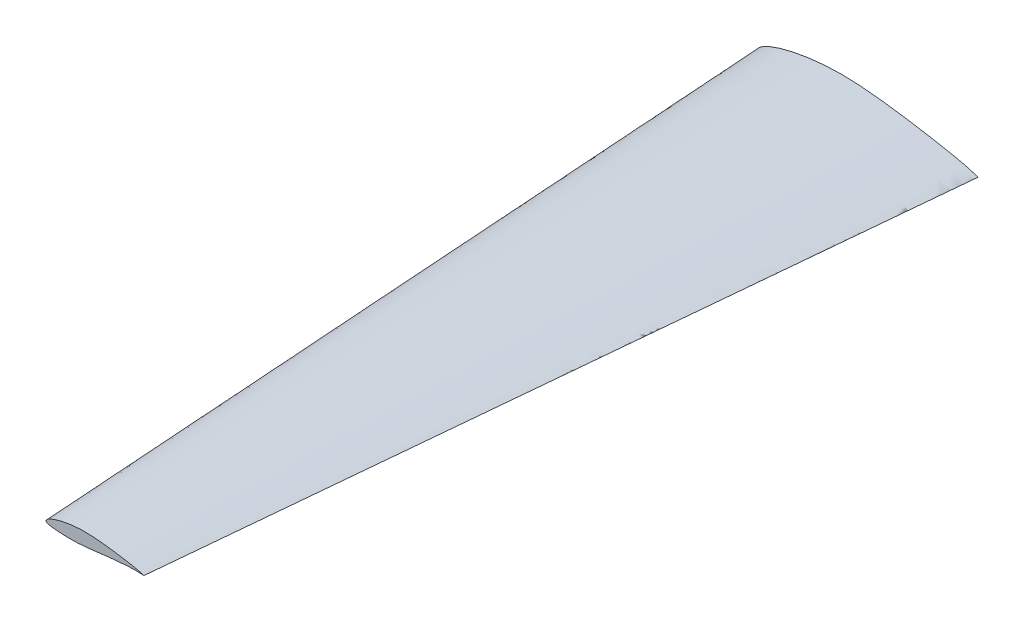
SolidWorks part; units mm, degrees
ref_plane "Front Plane" through (0, 0, 0) normal (0, 0, 1) x (1, 0, 0)
ref_plane "Top Plane" through (0, 0, 0) normal (0, 1, 0) x (1, 0, 0)
ref_plane "Right Plane" through (0, 0, 0) normal (1, 0, 0) x (0, 0, -1)
curve "Curve1"
  spline degree 3 poles (0.9921, 0.0008, 0) (1.0019, -0.0008, 0) (0.9929, 0.0016, 0) (0.9861, 0.0043, 0) (0.9706, 0.0096, 0) (0.9519, 0.0152, 0) (0.9278, 0.021, 0) (0.8992, 0.0273, 0) (0.8662, 0.0341, 0) (0.8293, 0.0413, 0) (0.789, 0.0488, 0) (0.746, 0.0564, 0) (0.7007, 0.0641, 0) (0.6538, 0.0714, 0) (0.6058, 0.0784, 0) (0.5573, 0.0846, 0) (0.5088, 0.0898, 0) (0.4609, 0.0938, 0) (0.4138, 0.0961, 0) (0.3679, 0.0966, 0) (0.3232, 0.0952, 0) (0.2801, 0.092, 0) (0.2388, 0.0874, 0) (0.1997, 0.0815, 0) (0.1631, 0.0746, 0) (0.1296, 0.0669, 0) (0.0993, 0.0585, 0) (0.0726, 0.0496, 0) (0.0499, 0.0404, 0) (0.0312, 0.031, 0) (0.0168, 0.0217, 0) (0.0085, 0.0145, 0) (0.0039, 0.009, 0) (0.0018, 0.0058, 0) (0.0004, 0.0024, 0) (0, 0.0003, 0) (0, -0.0012, 0) (0.0006, -0.0026, 0) (0.002, -0.0043, 0) (0.0049, -0.007, 0) (0.0107, -0.0108, 0) (0.0215, -0.0156, 0) (0.0378, -0.0206, 0) (0.0598, -0.0253, 0) (0.0864, -0.0294, 0) (0.1174, -0.033, 0) (0.1523, -0.036, 0) (0.1908, -0.0383, 0) (0.2323, -0.0397, 0) (0.2764, -0.0402, 0) (0.3228, -0.0395, 0) (0.3711, -0.0373, 0) (0.4212, -0.0335, 0) (0.4729, -0.0284, 0) (0.526, -0.0227, 0) (0.5798, -0.0169, 0) (0.6336, -0.0114, 0) (0.6866, -0.0064, 0) (0.7378, -0.0023, 0) (0.7866, 0.0009, 0) (0.832, 0.0031, 0) (0.8733, 0.0042, 0) (0.9096, 0.0045, 0) (0.9406, 0.0038, 0) (0.9645, 0.0029, 0) (0.984, 0.0013, 0) (0.9921, 0.0008, 0) (1.0019, -0.0008, 0) (0.9929, 0.0016, 0) knots -0.016161 -0.007282 -0.001839 0 0.00178 0.006777 0.014308 0.024046 0.036116 0.050547 0.06713 0.085624 0.105767 0.127282 0.149864 0.17323 0.197069 0.221103 0.245052 0.268663 0.291773 0.314299 0.336178 0.357377 0.377792 0.397225 0.415489 0.432417 0.447849 0.461651 0.473687 0.483898 0.492263 0.498797 0.499955 0.502811 0.504371 0.50536 0.505925 0.506503 0.507535 0.509205 0.512345 0.517665 0.526422 0.537425 0.550643 0.565966 0.583206 0.602155 0.622587 0.644255 0.666998 0.690703 0.715307 0.740824 0.767084 0.793717 0.820331 0.846519 0.871863 0.895937 0.918335 0.938667 0.956573 0.971715 0.983839 0.992718 0.998161 1 1.00178 1.006777 1.014308 periodic
sketch "Sketch1" plane through (0, 0, 0) normal (0, 0, 1) x (1, 0, 0)
  line L0 (637.2059, -30.8288) -> (-1162.7941, -35.0845) construction
  spline S1 degree 3 poles (622.967, -28.64) (640.692, -31.5786) (624.3406, -27.283) (612.1808, -22.4384) (584.1935, -12.9236) (550.5734, -3.0031) (507.0318, 7.3176) (455.5452, 18.4128) (396.0453, 30.4121) (329.6088, 43.1368) (257.1037, 56.3698) (179.566, 69.8812) (98.004, 83.2872) (13.4916, 96.2742) (-72.9444, 108.4165) (-160.2766, 119.2439) (-247.5248, 128.3611) (-333.8508, 135.2066) (-418.6228, 139.0501) (-501.3609, 139.671) (-581.7163, 136.8854) (-659.2966, 130.868) (-733.6064, 122.2205) (-804.0052, 111.4712) (-869.743, 98.8183) (-930.1494, 84.6626) (-984.6043, 69.3092) (-1032.5261, 53.0959) (-1073.4471, 36.3919) (-1106.9728, 19.4367) (-1132.8144, 2.6523) (-1147.698, -10.4496) (-1155.9379, -20.4072) (-1159.736, -26.142) (-1162.2969, -32.2888) (-1163.0296, -36.0635) (-1162.8865, -38.7086) (-1161.8222, -41.1954) (-1159.3385, -44.3902) (-1154.0434, -49.2445) (-1143.5465, -55.9865) (-1124.1742, -64.4963) (-1094.6997, -73.385) (-1055.1419, -81.7565) (-1007.2196, -89.0072) (-951.47, -95.2724) (-888.5578, -100.3967) (-819.2858, -104.233) (-744.5209, -106.6291) (-665.0686, -107.2277) (-581.6186, -105.541) (-494.6577, -101.2591) (-404.4744, -94.1471) (-311.3767, -84.5976) (-215.8933, -74.0273) (-119.0803, -63.2443) (-22.3001, -52.9711) (72.9936, -43.6696) (165.2978, -35.8585) (253.0846, -29.787) (334.8123, -25.5512) (409.125, -23.2681) (474.3717, -22.626) (530.1728, -23.5565) (573.2061, -25.0278) (608.3968, -27.7924) (622.967, -28.64) (640.692, -31.5786) (624.3406, -27.283) knots -0.016161 -0.007282 -0.001839 0 0.00178 0.006777 0.014308 0.024046 0.036116 0.050547 0.06713 0.085624 0.105767 0.127282 0.149864 0.17323 0.197069 0.221103 0.245052 0.268663 0.291773 0.314299 0.336178 0.357377 0.377792 0.397225 0.415489 0.432417 0.447849 0.461651 0.473687 0.483898 0.492263 0.498797 0.499955 0.502811 0.504371 0.50536 0.505925 0.506503 0.507535 0.509205 0.512345 0.517665 0.526422 0.537425 0.550643 0.565966 0.583206 0.602155 0.622587 0.644255 0.666998 0.690703 0.715307 0.740824 0.767084 0.793717 0.820331 0.846519 0.871863 0.895937 0.918335 0.938667 0.956573 0.971715 0.983839 0.992718 0.998161 1 1.00178 1.006777 1.014308 only from (637.2059, -30.8288) to (637.2059, -30.8288)
  dimension "D1" = 1800
ref_plane "Plane1" through (0, 0, 6200) normal (0, 0, 1) x (1, 0, 0)
ref_plane "Plane3" through (0, -35.0845, 0) normal (0, 1, 0) x (1, 0, 0)
sketch "Sketch4" plane through (0, -35.0845, 0) normal (0, 1, 0) x (1, 0, 0)
  line L1 (637.2059, 0) -> (-1162.7941, 0) construction
  line L2 (-172.1886, -6200) -> (172.1886, -6200) construction
  line L4 (-1162.7941, 0) -> (-862.7941, -6200)
sketch "Sketch5" plane through (0, 0, 6200) normal (0, 0, 1) x (1, 0, 0)
  line L0 (46.251, -35.2354) -> (-753.7688, -35.3009) construction
  spline S1 degree 3 poles (39.9103, -34.3504) (47.78, -35.5469) (40.5107, -33.741) (35.0952, -31.6671) (22.6402, -27.6181) (7.6874, -23.4229) (-11.663, -19.1093) (-34.5377, -14.4998) (-60.9677, -9.5373) (-90.4749, -4.2947) (-122.6736, 1.1372) (-157.1033, 6.6624) (-193.3153, 12.1171) (-230.8318, 17.3686) (-269.1955, 22.2345) (-307.9483, 26.5125) (-346.6538, 30.0335) (-384.9373, 32.5536) (-422.5145, 33.7529) (-459.1715, 33.5367) (-494.7528, 31.8256) (-529.0855, 28.6992) (-561.9538, 24.4271) (-593.0769, 19.2472) (-622.124, 13.2516) (-648.8002, 6.6219) (-672.8329, -0.5031) (-693.9662, -7.9701) (-711.9952, -15.6131) (-726.7466, -23.3233) (-738.0949, -30.9123) (-744.6106, -36.8049) (-748.2018, -41.2651) (-749.8503, -43.8282) (-750.9483, -46.5664) (-751.2505, -48.243) (-751.1714, -49.4139) (-750.6851, -50.5093) (-749.5659, -51.9099) (-747.1913, -54.0289) (-742.5011, -56.9533) (-733.8685, -60.6082) (-720.7584, -64.3709) (-703.1844, -67.8447) (-681.9116, -70.7722) (-657.1771, -73.2167) (-629.2762, -75.1133) (-598.5656, -76.4015) (-565.4302, -77.0191) (-530.2289, -76.8125) (-493.2702, -75.5698) (-454.7715, -73.1566) (-414.8621, -69.4706) (-373.6761, -64.6873) (-331.4393, -59.4377) (-288.6147, -54.086) (-245.8016, -48.9603) (-203.6413, -44.2739) (-162.7964, -40.2655) (-123.9425, -37.0546) (-87.7619, -34.6929) (-54.8546, -33.2402) (-25.9538, -32.5684) (-1.2281, -32.6493) (17.8446, -33.0456) (33.4506, -34.0614) (39.9103, -34.3504) (47.78, -35.5469) (40.5107, -33.741) knots -0.016161 -0.007282 -0.001839 0 0.00178 0.006777 0.014308 0.024046 0.036116 0.050547 0.06713 0.085624 0.105767 0.127282 0.149864 0.17323 0.197069 0.221103 0.245052 0.268663 0.291773 0.314299 0.336178 0.357377 0.377792 0.397225 0.415489 0.432417 0.447849 0.461651 0.473687 0.483898 0.492263 0.498797 0.499955 0.502811 0.504371 0.50536 0.505925 0.506503 0.507535 0.509205 0.512345 0.517665 0.526422 0.537425 0.550643 0.565966 0.583206 0.602155 0.622587 0.644255 0.666998 0.690703 0.715307 0.740824 0.767084 0.793717 0.820331 0.846519 0.871863 0.895937 0.918335 0.938667 0.956573 0.971715 0.983839 0.992718 0.998161 1 1.00178 1.006777 1.014308 only from (46.2312, -35.2354) to (46.2312, -35.2354)
  dimension "D1" = 800
sketch "Sketch6" plane through (0, 0, 6200) normal (0, 0, 1) x (1, 0, 0)
  line L0 (-753.7688, -35.3009) -> (-751.2083, -48.6103)
  spline S0 degree 3 poles (39.9103, -34.3504) (47.78, -35.5469) (40.5107, -33.741) (35.0952, -31.6671) (22.6402, -27.6181) (7.6874, -23.4229) (-11.663, -19.1093) (-34.5377, -14.4998) (-60.9677, -9.5373) (-90.4749, -4.2947) (-122.6736, 1.1372) (-157.1033, 6.6624) (-193.3153, 12.1171) (-230.8318, 17.3686) (-269.1955, 22.2345) (-307.9483, 26.5125) (-346.6538, 30.0335) (-384.9373, 32.5536) (-422.5145, 33.7529) (-459.1715, 33.5367) (-494.7528, 31.8256) (-529.0855, 28.6992) (-561.9538, 24.4271) (-593.0769, 19.2472) (-622.124, 13.2516) (-648.8002, 6.6219) (-672.8329, -0.5031) (-693.9662, -7.9701) (-711.9952, -15.6131) (-726.7466, -23.3233) (-738.0949, -30.9123) (-744.6106, -36.8049) (-748.2018, -41.2651) (-749.8503, -43.8282) (-750.9483, -46.5664) (-751.2505, -48.243) (-751.1714, -49.4139) (-750.6851, -50.5093) (-749.5659, -51.9099) (-747.1913, -54.0289) (-742.5011, -56.9533) (-733.8685, -60.6082) (-720.7584, -64.3709) (-703.1844, -67.8447) (-681.9116, -70.7722) (-657.1771, -73.2167) (-629.2762, -75.1133) (-598.5656, -76.4015) (-565.4302, -77.0191) (-530.2289, -76.8125) (-493.2702, -75.5698) (-454.7715, -73.1566) (-414.8621, -69.4706) (-373.6761, -64.6873) (-331.4393, -59.4377) (-288.6147, -54.086) (-245.8016, -48.9603) (-203.6413, -44.2739) (-162.7964, -40.2655) (-123.9425, -37.0546) (-87.7619, -34.6929) (-54.8546, -33.2402) (-25.9538, -32.5684) (-1.2281, -32.6493) (17.8446, -33.0456) (33.4506, -34.0614) (39.9103, -34.3504) (47.78, -35.5469) (40.5107, -33.741) knots -0.016161 -0.007282 -0.001839 0 0.00178 0.006777 0.014308 0.024046 0.036116 0.050547 0.06713 0.085624 0.105767 0.127282 0.149864 0.17323 0.197069 0.221103 0.245052 0.268663 0.291773 0.314299 0.336178 0.357377 0.377792 0.397225 0.415489 0.432417 0.447849 0.461651 0.473687 0.483898 0.492263 0.498797 0.499955 0.502811 0.504371 0.50536 0.505925 0.506503 0.507535 0.509205 0.512345 0.517665 0.526422 0.537425 0.550643 0.565966 0.583206 0.602155 0.622587 0.644255 0.666998 0.690703 0.715307 0.740824 0.767084 0.793717 0.820331 0.846519 0.871863 0.895937 0.918335 0.938667 0.956573 0.971715 0.983839 0.992718 0.998161 1 1.00178 1.006777 1.014308 only from (46.2312, -35.2354) to (46.2312, -35.2354) construction
ref_axis "Axis2" through (-751.2083, -48.6103, 6200) along (-0.0662, 0.0022, -0.9978)
loft "Loft5" add profiles "Sketch1", "Sketch5" connector at (-1162.9043, -36.0103, 0) connector at (-751.1274, -47.6465, 6200)
sketch "Sketch7" plane through (0, 0, 0) normal (0, 0, -1) x (-1, 0, 0)
  line L1 (378.6621, 100.8715) -> (605.0337, 100.8715)
  line L2 (378.6621, 100.8715) -> (378.6621, -50.9306)
  line L3 (378.6621, -50.9306) -> (605.0337, -50.9306)
  line L4 (605.0337, 100.8715) -> (605.0337, -50.9306)
extrude "Boss-Extrude1" add sketch "Sketch7" along normal blind 10
